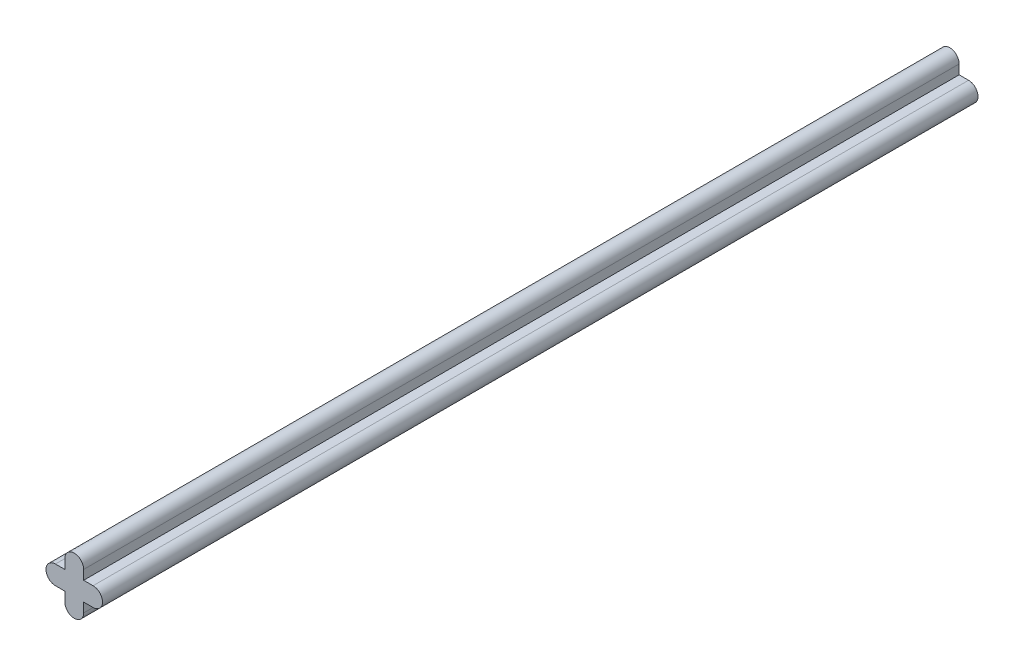
SolidWorks part; units mm, degrees
material "PVC Rigid"
ref_plane "Front Plane" through (0, 0, 0) normal (0, 0, 1) x (1, 0, 0)
ref_plane "Top Plane" through (0, 0, 0) normal (0, 1, 0) x (1, 0, 0)
ref_plane "Right Plane" through (0, 0, 0) normal (1, 0, 0) x (0, 0, -1)
sketch "Sketch1" plane through (0, 0, 0) normal (0, 0, 1) x (1, 0, 0)
  line L0 (-1.524, 0) -> (1.524, 0) construction
  line L1 (-1.524, 0.762) -> (1.524, 0.762)
  line L2 (-1.524, -0.762) -> (1.524, -0.762)
  line L8 (0, 1.524) -> (0, -1.524) construction
  line L9 (0.762, 1.524) -> (0.762, -1.524)
  line L10 (-0.762, 1.524) -> (-0.762, -1.524)
  arc A0 (-1.524, 0.762) -> (-1.524, -0.762) centre (-1.524, 0) ccw
  arc A2 (1.524, -0.762) -> (1.524, 0.762) centre (1.524, 0) ccw
  arc A4 (0.762, 1.524) -> (-0.762, 1.524) centre (0, 1.524) ccw
  arc A5 (-0.762, -1.524) -> (0.762, -1.524) centre (0, -1.524) ccw
  circle A7 centre (0, 0) radius 2.286 construction
  point P1 (3.81, 0)
  point P3 (0, 0)
  point P8 (0, 0)
  point P13 (5.334, 0)
  point P15 (7.62, 0)
  point P17 (0, 3.302)
  point P18 (19.05, 3.302)
  point P19 (0, -3.302)
  point P20 (19.05, -3.302)
  point P23 (13.843, 0)
  point P24 (3.81, 0)
  point P25 (23.368, 0)
  point P26 (3.429, 0)
  point P27 (-7.874, -3.302)
  point P28 (7.874, -3.302)
  point P29 (-7.874, 3.302)
  point P30 (7.874, 3.302)
  point P35 (11.811, 0)
  point P60 (11.5175, 1.1139)
  dimension "D2" = 1.524
  dimension "D3" = 4.572
  dimension "D1" = 1.524
extrude "Boss-Extrude1" add sketch "Sketch1" along normal blind 70.866 contours L1 A0 L2 L10 | L9 A4 L10 L1 | L2 A2 L1 L9 | L10 A5 L9 L2 | L1 L10 L2 L9 region at (-1.4529, 0, 0) region at (0, 1.4529, 0) region at (0, 0, 0) region at (1.4529, 0, 0) region at (0, -1.4529, 0)
sketch "Sketch2" plane through (0, 0, 0) normal (0, 0, -1) x (-1, 0, 0)
  circle A0 centre (0, 0) radius 2.286
sketch "Sketch3" plane through (0, 0, 70.866) normal (0, 0, 1) x (1, 0, 0)
  circle A0 centre (0, 0) radius 2.286 construction
  circle A1 centre (0, 0) radius 2.286
ref_plane "Plane1" through (0, 0, 35.433) normal (0, 0, -1) x (-1, 0, 0)
sketch "Sketch4" plane through (0, 0, 35.433) normal (0, 0, -1) x (-1, 0, 0)
  circle A0 centre (0, 0) radius 2.286 construction
  circle A1 centre (0, 0) radius 2.286
ref_plane "Plane2" through (0, 0, 13.589) normal (0, 0, 1) x (1, 0, 0)
sketch "Sketch5" plane through (0, 0, 13.589) normal (0, 0, 1) x (1, 0, 0)
  point P0 (0, 0)
